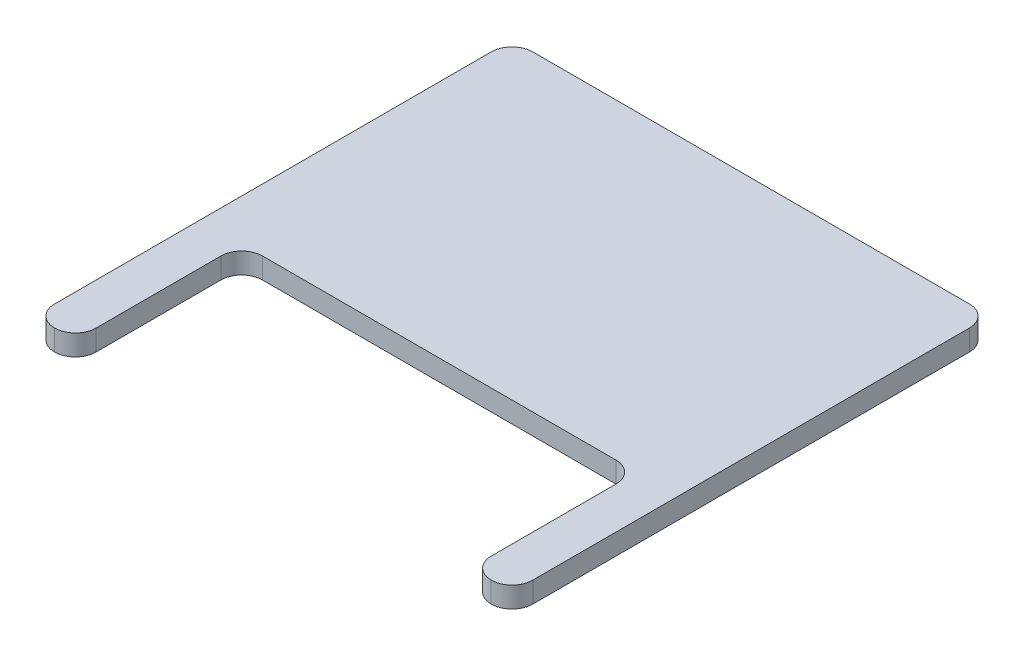
SolidWorks part; units mm, degrees
material "6061 Alloy"
ref_plane "Front Plane" through (0, 0, 0) normal (0, 0, 1) x (1, 0, 0)
ref_plane "Top Plane" through (0, 0, 0) normal (0, 1, 0) x (1, 0, 0)
ref_plane "Right Plane" through (0, 0, 0) normal (1, 0, 0) x (0, 0, -1)
sketch "Sketch1" plane through (0, 0, 0) normal (0, 1, 0) x (1, 0, 0)
  line L0 (0, -146.05) -> (-12.7, -146.05)
  line L13 (0, 0) -> (-146.05, 0)
  line L14 (0, 0) -> (0, -146.05)
  line L15 (0, -146.05) -> (-12.7, -146.05)
  line L16 (-146.05, 0) -> (-146.05, -146.05)
  line L17 (-12.7, -146.05) -> (-12.7, -95.25)
  line L18 (-12.7, -95.25) -> (-133.35, -95.25)
  line L19 (-133.35, -95.25) -> (-133.35, -146.05)
  line L20 (-133.35, -146.05) -> (-146.05, -146.05)
  dimension "D1" = 146.05
  dimension "D2" = 146.05
  dimension "D3" = 12.7
  dimension "D4" = 12.7
  dimension "D5" = 50.8
extrude "Boss-Extrude1" add sketch "Sketch1" along normal blind 6.35 contours L20 L19 L18 L17 L0 L14 L13 L16 region at (-73.025, 0, 53.8234)
fillet "Fillet1" radius 6.35 8 edges at (-12.7, 3.175, 95.25) (-133.35, 3.175, 95.25) (0, 3.175, 146.05) (-146.05, 3.175, 0) (0, 3.175, 0) (-12.7, 3.175, 146.05) (-146.05, 3.175, 146.05) (-133.35, 3.175, 146.05)
